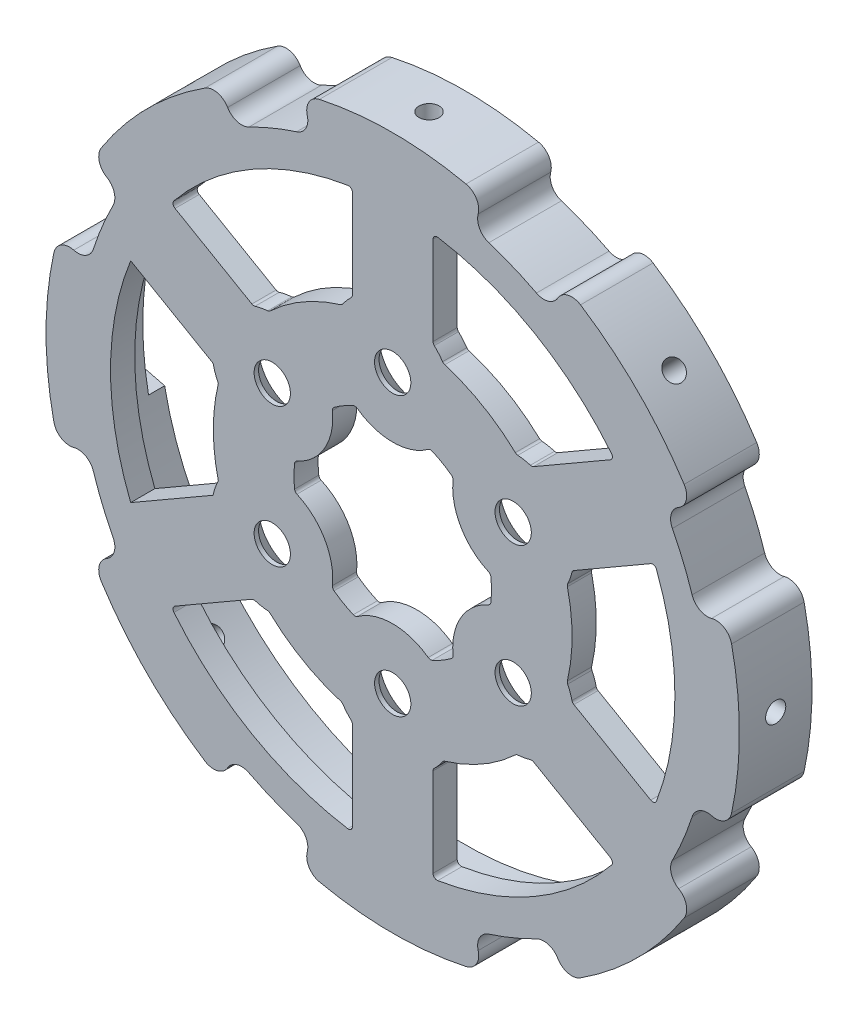
SolidWorks part; units mm, degrees
ref_plane "前视基准面" through (0, 0, 0) normal (0, 0, 1) x (1, 0, 0)
ref_plane "上视基准面" through (0, 0, 0) normal (0, 1, 0) x (1, 0, 0)
ref_plane "右视基准面" through (0, 0, 0) normal (1, 0, 0) x (0, 0, -1)
sketch "草图1" plane through (0, 0, 0) normal (0, 0, 1) x (1, 0, 0)
  line L16 (21.5, 37.2391) -> (19.5, 33.775)
  line L17 (11.1292, 41.5348) -> (10.0939, 37.6711)
  line L18 (-11.1292, 41.5348) -> (-10.0939, 37.6711)
  line L19 (37.2391, 21.5) -> (33.775, 19.5)
  line L20 (41.5348, 11.1292) -> (37.6711, 10.0939)
  line L21 (41.5348, -11.1292) -> (37.6711, -10.0939)
  line L22 (37.2391, -21.5) -> (33.775, -19.5)
  line L23 (21.5, -37.2391) -> (19.5, -33.775)
  line L24 (11.1292, -41.5348) -> (10.0939, -37.6711)
  line L25 (-11.1292, -41.5348) -> (-10.0939, -37.6711)
  line L26 (-21.5, -37.2391) -> (-19.5, -33.775)
  line L27 (-37.2391, -21.5) -> (-33.775, -19.5)
  line L28 (-41.5348, -11.1292) -> (-37.6711, -10.0939)
  line L29 (-41.5348, 11.1292) -> (-37.6711, 10.0939)
  line L30 (-37.2391, 21.5) -> (-33.775, 19.5)
  line L31 (-21.5, 37.2391) -> (-19.5, 33.775)
  circle A1 centre (0, 0) radius 38
  arc A6 (0, 43) -> (-11.1292, 41.5348) centre (0, 0) ccw
  arc A31 (0, 43) -> (11.1292, 41.5348) centre (0, 0) cw
  arc A32 (10.0939, 37.6711) -> (19.5, 33.775) centre (0, 0) cw
  arc A33 (30.4056, 30.4056) -> (21.5, 37.2391) centre (0, 0) ccw
  arc A34 (30.4056, 30.4056) -> (37.2391, 21.5) centre (0, 0) cw
  arc A35 (33.775, 19.5) -> (37.6711, 10.0939) centre (0, 0) cw
  arc A36 (43, 0) -> (41.5348, 11.1292) centre (0, 0) ccw
  arc A37 (43, 0) -> (41.5348, -11.1292) centre (0, 0) cw
  arc A38 (37.6711, -10.0939) -> (33.775, -19.5) centre (0, 0) cw
  arc A39 (30.4056, -30.4056) -> (37.2391, -21.5) centre (0, 0) ccw
  arc A40 (30.4056, -30.4056) -> (21.5, -37.2391) centre (0, 0) cw
  arc A41 (19.5, -33.775) -> (10.0939, -37.6711) centre (0, 0) cw
  arc A42 (0, -43) -> (11.1292, -41.5348) centre (0, 0) ccw
  arc A43 (0, -43) -> (-11.1292, -41.5348) centre (0, 0) cw
  arc A44 (-10.0939, -37.6711) -> (-19.5, -33.775) centre (0, 0) cw
  arc A45 (-30.4056, -30.4056) -> (-21.5, -37.2391) centre (0, 0) ccw
  arc A46 (-30.4056, -30.4056) -> (-37.2391, -21.5) centre (0, 0) cw
  arc A47 (-33.775, -19.5) -> (-37.6711, -10.0939) centre (0, 0) cw
  arc A48 (-43, 0) -> (-41.5348, -11.1292) centre (0, 0) ccw
  arc A49 (-43, 0) -> (-41.5348, 11.1292) centre (0, 0) cw
  arc A50 (-37.6711, 10.0939) -> (-33.775, 19.5) centre (0, 0) cw
  arc A51 (-30.4056, 30.4056) -> (-37.2391, 21.5) centre (0, 0) ccw
  arc A52 (-30.4056, 30.4056) -> (-21.5, 37.2391) centre (0, 0) cw
  arc A53 (-19.5, 33.775) -> (-10.0939, 37.6711) centre (0, 0) cw
  point P55 (0, 0)
  point P56 (0, 0)
  dimension "D1" = 8
extrude "凸台-拉伸1" add sketch "草图1" against normal blind 6
sketch "草图2" plane through (0, 0, 0) normal (0, 0, 1) x (1, 0, 0)
  line L16 (-11.1292, 41.5348) -> (-10.0939, 37.6711)
  line L17 (10.0939, 37.6711) -> (11.1292, 41.5348)
  line L18 (21.5, 37.2391) -> (19.5, 33.775)
  line L19 (33.775, 19.5) -> (37.2391, 21.5)
  line L20 (41.5348, 11.1292) -> (37.6711, 10.0939)
  line L21 (37.6711, -10.0939) -> (41.5348, -11.1292)
  line L22 (37.2391, -21.5) -> (33.775, -19.5)
  line L23 (19.5, -33.775) -> (21.5, -37.2391)
  line L24 (11.1292, -41.5348) -> (10.0939, -37.6711)
  line L25 (-10.0939, -37.6711) -> (-11.1292, -41.5348)
  line L26 (-21.5, -37.2391) -> (-19.5, -33.775)
  line L27 (-33.775, -19.5) -> (-37.2391, -21.5)
  line L28 (-41.5348, -11.1292) -> (-37.6711, -10.0939)
  line L29 (-37.6711, 10.0939) -> (-41.5348, 11.1292)
  line L30 (-37.2391, 21.5) -> (-33.775, 19.5)
  line L31 (-19.5, 33.775) -> (-21.5, 37.2391)
  arc A27 (0, 43) -> (11.1292, 41.5348) centre (0, 0) cw
  arc A28 (10.0939, 37.6711) -> (19.5, 33.775) centre (0, 0) cw
  arc A29 (0, 43) -> (-11.1292, 41.5348) centre (0, 0) ccw
  arc A30 (30.4056, 30.4056) -> (21.5, 37.2391) centre (0, 0) ccw
  arc A31 (30.4056, 30.4056) -> (37.2391, 21.5) centre (0, 0) cw
  arc A32 (33.775, 19.5) -> (37.6711, 10.0939) centre (0, 0) cw
  arc A33 (43, 0) -> (41.5348, 11.1292) centre (0, 0) ccw
  arc A34 (43, 0) -> (41.5348, -11.1292) centre (0, 0) cw
  arc A35 (37.6711, -10.0939) -> (33.775, -19.5) centre (0, 0) cw
  arc A36 (30.4056, -30.4056) -> (37.2391, -21.5) centre (0, 0) ccw
  arc A37 (30.4056, -30.4056) -> (21.5, -37.2391) centre (0, 0) cw
  arc A38 (19.5, -33.775) -> (10.0939, -37.6711) centre (0, 0) cw
  arc A39 (0, -43) -> (11.1292, -41.5348) centre (0, 0) ccw
  arc A40 (0, -43) -> (-11.1292, -41.5348) centre (0, 0) cw
  arc A41 (-10.0939, -37.6711) -> (-19.5, -33.775) centre (0, 0) cw
  arc A42 (-30.4056, -30.4056) -> (-21.5, -37.2391) centre (0, 0) ccw
  arc A43 (-30.4056, -30.4056) -> (-37.2391, -21.5) centre (0, 0) cw
  arc A44 (-33.775, -19.5) -> (-37.6711, -10.0939) centre (0, 0) cw
  arc A45 (-43, 0) -> (-41.5348, -11.1292) centre (0, 0) ccw
  arc A46 (-43, 0) -> (-41.5348, 11.1292) centre (0, 0) cw
  arc A47 (-37.6711, 10.0939) -> (-33.775, 19.5) centre (0, 0) cw
  arc A48 (-30.4056, 30.4056) -> (-37.2391, 21.5) centre (0, 0) ccw
  arc A49 (-30.4056, 30.4056) -> (-21.5, 37.2391) centre (0, 0) cw
  arc A50 (-19.5, 33.775) -> (-10.0939, 37.6711) centre (0, 0) cw
  point P43 (0, 0)
extrude "凸台-拉伸2" add sketch "草图2" along normal blind 3
sketch "草图12" plane through (0, 0, 0) normal (0, 0, 1) x (1, 0, 0)
  circle A0 centre (0, 0) radius 17.25 construction
  circle A1 centre (0, 17.25) radius 2
  circle A2 centre (14.9389, 8.625) radius 2
  circle A3 centre (14.9389, -8.625) radius 2
  circle A4 centre (0, -17.25) radius 2
  circle A5 centre (-14.9389, -8.625) radius 2
  circle A6 centre (-14.9389, 8.625) radius 2
  point P17 (0, 0)
  dimension "D1" = 34.5
  dimension "D2" = 4
hole_wizard "M4 锥坑平头的锥孔1" positions "3D草图2" profile "草图4" countersink size "M4" standard "BSI" end condition through all
sketch3d "3D草图2"
  point P131 (0, 17.25, 0)
  point P134 (14.9389, 8.625, 0)
  point P137 (14.9389, -8.625, 0)
  point P140 (0, -17.25, 0)
  point P143 (-14.9389, -8.625, 0)
  point P150 (-14.9389, 8.625, 0)
sketch "草图4" plane through (0, 17.25, 0) normal (1, 0, 0) x (0, 1, 0)
  line L0 (0, 0) -> (0, 3)
  line L1 (0, 3) -> (2.25, 3)
  line L2 (2.25, 3) -> (2.25, 2.45)
  line L3 (2.25, 2.45) -> (4.7, 0)
  line L5 (4.7, 0) -> (0, 0)
  line L6 (-2.25, 2.45) -> (-4.7, 0) construction
  line L11 (0, -6.35) -> (0, 107.95) construction
  dimension "通孔孔直径" = 4.5
  dimension "通孔孔深度" = 3
  dimension "近端锥形沉头孔直径" = 9.4
  dimension "近端锥形沉头孔角度" = 90
hole_wizard "M3 螺纹孔1" positions "3D草图3" profile "草图5" tap size "M3" standard "GB" end condition up to next
sketch3d "3D草图3"
  point P5 (0, -43, -1.5)
  point P13 (30.4056, -30.4056, -1.5)
  point P33 (30.4056, 30.4056, -1.5)
  point P43 (43, 0, -1.5)
  point P53 (-30.4056, 30.4056, -1.5)
  point P55 (-30.4056, -30.4056, -1.5)
  point P57 (43, 0, -1.5)
  point P72 (-43, 0, -1.5)
  point P77 (0, 43, -1.5)
sketch "草图5" plane through (0, -43, -1.5) normal (1, 0, 0) x (0, 0, -1)
  line L0 (0, 0) -> (0, 5)
  line L1 (0, 5) -> (1.25, 5)
  line L2 (1.25, 5) -> (1.25, 0)
  line L5 (1.25, 0) -> (0, 0)
  line L11 (0, -6.35) -> (0, 107.95) construction
  dimension "通孔螺纹孔钻头直径" = 2.5
  dimension "通孔螺纹孔钻头深度" = 5
cosmetic thread "孔螺蚊线1" parameters "D2"=3
cosmetic thread "孔螺蚊线2" parameters "D2"=3
cosmetic thread "孔螺蚊线3" parameters "D2"=3
cosmetic thread "孔螺蚊线4" parameters "D2"=3
cosmetic thread "孔螺蚊线5" parameters "D2"=3
cosmetic thread "孔螺蚊线6" parameters "D2"=3
sketch "草图6" plane through (0, 0, 0) normal (0, 0, 1) x (1, 0, 0)
  line L3 (-18.2637, -1.8566) -> (-18.2637, 1.8566)
  line L4 (-18.2637, 1.8566) -> (-21.0076, 1.8566)
  line L13 (-18.2637, -1.8566) -> (-20.5637, -1.8566)
  line L21 (-20.5637, -9.7163) -> (-20.5637, -1.8566)
  line L22 (-42.5793, 6) -> (-34.6246, 8)
  line L23 (-42.5793, -6) -> (-34.6246, -8)
  line L24 (-21.0076, 1.8566) -> (-21.0076, 9.7163)
  line L25 (-34.6246, 8) -> (-30.6246, 8)
  line L26 (-21.0076, 9.7163) -> (-27.8188, 9.7163)
  line L27 (-30.6246, 8) -> (-27.8188, 9.7163)
  line L28 (-34.6246, -8) -> (-30.6246, -8)
  line L29 (-30.6246, -8) -> (-29.0922, -9.7163)
  line L30 (-29.0922, -9.7163) -> (-20.5637, -9.7163)
  line L31 (0, 0) -> (-18.2637, 0) construction
  line L32 (-18.2637, 0) -> (-32.358, 0) construction
  arc A2 (-41.5348, 11.1292) -> (-41.5348, -11.1292) centre (0, 0) ccw construction
  arc A3 (-42.5793, 6) -> (-42.5793, -6) centre (0, 0) ccw
extrude "切除-拉伸1" cut sketch "草图6" along normal blind 3 from surface starting at face at (38, 0, -6)
sketch "草图9" plane through (0, 0, 0) normal (0, 0, 1) x (1, 0, 0)
  line L2 (-42.5793, 6) -> (-37.2862, 7.3308)
  line L3 (-42.5793, -6) -> (-37.2862, -7.3308)
  arc A0 (-37.2862, -7.3308) -> (-37.2862, 7.3308) centre (0, 0) cw
  arc A1 (-42.5793, -6) -> (-42.5793, 6) centre (0, 0) cw
extrude "凸台-拉伸3" add sketch "草图9" against normal blind 1 from surface starting at face at (-40.2164, 0, -3)
fillet "圆角1" radius 2 32 edges at (-21.5, 37.2391, -1.5) (-37.6711, 10.0939, -1.5) (-37.2391, 21.5, -1.5) (-33.775, 19.5, -1.5) (-41.5348, 11.1292, -1.5) (-37.2391, -21.5, -1.5) (-33.775, -19.5, -1.5) (-37.6711, -10.0939, -1.5) (-41.5348, -11.1292, -1.5) (-21.5, -37.2391, -1.5) (-19.5, -33.775, -1.5) (-11.1292, -41.5348, -1.5) (-10.0939, -37.6711, -1.5) (21.5, -37.2391, -1.5) (11.1292, -41.5348, -1.5) (10.0939, -37.6711, -1.5) (19.5, -33.775, -1.5) (37.2391, -21.5, -1.5) (33.775, -19.5, -1.5) (37.6711, 10.0939, -1.5) (37.6711, -10.0939, -1.5) (41.5348, -11.1292, -1.5) (41.5348, 11.1292, -1.5) (33.775, 19.5, -1.5) (37.2391, 21.5, -1.5) (10.0939, 37.6711, -1.5) (21.5, 37.2391, -1.5) (19.5, 33.775, -1.5) (11.1292, 41.5348, -1.5) (-10.0939, 37.6711, -1.5) (-11.1292, 41.5348, -1.5) (-19.5, 33.775, -1.5)
sketch "草图11" plane through (0, 0, 0) normal (0, 0, 1) x (1, 0, 0)
  line L0 (0, 0) -> (0, 35) construction
  line L3 (0, 0) -> (14.9389, 8.625) construction
  line L4 (14.9389, 8.625) -> (30.3109, 17.5) construction
  line L7 (0, 0) -> (14.9389, -8.625) construction
  line L8 (14.9389, -8.625) -> (30.3109, -17.5) construction
  line L11 (0, 0) -> (0, -17.25) construction
  line L12 (0, -17.25) -> (0, -35) construction
  line L13 (0, 0) -> (-14.9389, 8.625) construction
  line L14 (-14.9389, 8.625) -> (-30.3109, 17.5) construction
  line L15 (0, 0) -> (-14.9389, -8.625) construction
  line L16 (-14.9389, -8.625) -> (-30.3109, -17.5) construction
  line L17 (5, 0) -> (5, 35)
  line L18 (17.4389, 4.2949) -> (32.8109, 13.1699)
  line L19 (12.4389, -12.9551) -> (27.8109, -21.8301)
  line L20 (-5, -17.25) -> (-5, -35)
  line L21 (-17.4389, -4.2949) -> (-32.8109, -13.1699)
  line L22 (-12.4389, 12.9551) -> (-27.8109, 21.8301)
  line L23 (-5, 0) -> (-5, 35)
  line L24 (12.4389, 12.9551) -> (27.8109, 21.8301)
  line L25 (17.4389, -4.2949) -> (32.8109, -13.1699)
  line L26 (5, -17.25) -> (5, -35)
  line L27 (-12.4389, -12.9551) -> (-27.8109, -21.8301)
  line L28 (-17.4389, 4.2949) -> (-32.8109, 13.1699)
  circle A30 centre (14.9389, 8.625) radius 7.5
  circle A31 centre (14.9389, -8.625) radius 7.5
  circle A32 centre (0, -17.25) radius 7.5
  circle A33 centre (-14.9389, -8.625) radius 7.5
  circle A34 centre (-14.9389, 8.625) radius 7.5
  circle A35 centre (0, 17.25) radius 7.5
  circle A36 centre (0, 0) radius 35
  circle A43 centre (0, 0) radius 22.25
  circle A44 centre (0, 0) radius 22.25
  circle A47 centre (0, 0) radius 12.25
  circle A48 centre (0, 0) radius 12.25
  point P14 (0, 0)
  dimension "D1" = 15
  dimension "D2" = 70
  dimension "D3" = 5
  dimension "D4" = 5
  dimension "D5" = 5
  dimension "D6" = 5
extrude "切除-拉伸2" cut sketch "草图11" along normal blind 10 contours A44 A35 L23 A36 L22 A34 | A44 A30 L24 A36 L17 A35 | A44 A31 L25 A36 L18 A30 | A44 A32 L26 A36 L19 A31 | A44 A33 L27 A36 L20 A32 | A30 A48 A35 A34 A33 A32 A31 | A44 A34 L28 A36 L21 A33 region at (0, 0, 0) region at (14.3899, 24.924, 0) region at (28.7797, 0, 0) region at (-14.3899, 24.924, 0) region at (14.3899, -24.924, 0) region at (-28.7797, 0, 0) region at (-14.3899, -24.924, 0)
fillet "圆角6" radius 0.5 42 edges at (17.2802, 15.7502, 1.5) (27.5, 21.6506, 1.5) (5, 34.641, 1.5) (5, 22.8402, 1.5) (6.2839, 21.3442, 1.5) (15.3427, 16.1141, 1.5) (22.2802, -7.09, 1.5) (32.5, -12.9904, 1.5) (32.5, 12.9904, 1.5) (22.2802, 7.09, 1.5) (21.6266, 5.2301, 1.5) (21.6266, -5.2301, 1.5) (5, -22.8402, 1.5) (5, -34.641, 1.5) (27.5, -21.6506, 1.5) (17.2802, -15.7502, 1.5) (15.3427, -16.1141, 1.5) (6.2839, -21.3442, 1.5) (-17.2802, -15.7502, 1.5) (-27.5, -21.6506, 1.5) (-5, -34.641, 1.5) (-5, -22.8402, 1.5) (-6.2839, -21.3442, 1.5) (-15.3427, -16.1141, 1.5) (-5, 22.8402, 1.5) (-27.5, 21.6506, 1.5) (-17.2802, 15.7502, 1.5) (-15.3427, 16.1141, 1.5) (-6.2839, 21.3442, 1.5) (4.6229, 11.3442, 1.5) (-4.6229, 11.3442, 1.5) (-7.5129, 9.6757, 1.5) (-12.1358, 1.6685, 1.5) (-12.1358, -1.6685, 1.5) (-7.5129, -9.6757, 1.5) (-4.6229, -11.3442, 1.5) (4.6229, -11.3442, 1.5) (7.5129, -9.6757, 1.5) (12.1358, -1.6685, 1.5) (12.1358, 1.6685, 1.5) (7.5129, 9.6757, 1.5) (-5, 34.641, 1.5)
